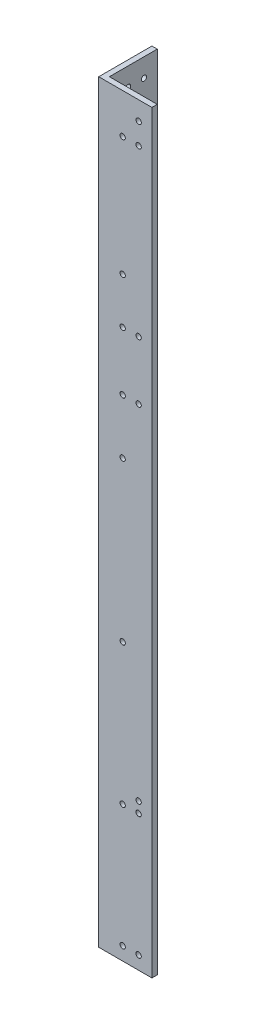
SolidWorks part; units mm, degrees
ref_plane "Front Plane" through (0, 0, 0) normal (0, 0, 1) x (1, 0, 0)
ref_plane "Top Plane" through (0, 0, 0) normal (0, 1, 0) x (1, 0, 0)
ref_plane "Right Plane" through (0, 0, 0) normal (1, 0, 0) x (0, 0, -1)
sketch "Sketch2" plane through (0, 0, 0) normal (0, 1, 0) x (1, 0, 0)
  line L0 (0, 31.75) -> (3.175, 31.75)
  line L1 (3.175, 31.75) -> (3.175, 3.175)
  line L2 (3.175, 3.175) -> (31.75, 3.175)
  line L3 (31.75, 3.175) -> (31.75, 0)
  line L4 (31.75, 0) -> (0, 0)
  line L5 (0, 0) -> (0, 31.75)
  point P9 (1.5875, 31.75)
  point P10 (31.75, 1.5875)
  dimension "D4" = 3.175
  dimension "D1" = 31.75
  dimension "D2" = 31.75
  dimension "D3" = 3.175
extrude "Boss-Extrude1" add sketch "Sketch2" along normal blind 450
sketch "LeftSideHoles-Sketch3" plane through (0, 0, 0) normal (0, 0, 1) x (1, 0, 0)
  line L0 (0, 0) -> (31.75, 0) construction
  line L1 (0, 450) -> (31.75, 450) construction
  line L3 (0, 450) -> (0, 0) construction
  circle A0 centre (14.2875, 81.1125) radius 1.5875
  circle A1 centre (23.8125, 81.1125) radius 1.5875
  circle A3 centre (23.8125, 87.4625) radius 1.5875
  circle A5 centre (14.2875, 426.1875) radius 1.5875
  circle A6 centre (23.8125, 438.8875) radius 1.5875
  circle A7 centre (23.8125, 426.1875) radius 1.5875
  circle A10 centre (14.2875, 327.6026) radius 1.5875
  circle A11 centre (23.8125, 327.6026) radius 1.5875
  circle A12 centre (14.2875, 292.6776) radius 1.5875
  circle A13 centre (23.8125, 292.6776) radius 1.5875
  circle A14 centre (14.2875, 7.9375) radius 1.5875
  circle A15 centre (23.8125, 7.9375) radius 1.5875
  circle A16 centre (14.2875, 165) radius 1.5875
  circle A17 centre (14.2875, 260) radius 1.5875
  circle A18 centre (14.2875, 355) radius 1.5875
  point P24 (15.875, 0)
  dimension "D4" = 3.175
  dimension "D1" = 81.1125
  dimension "D2" = 14.2875
  dimension "D10" = 7.9375
  dimension "D7" = 34.925
  dimension "D3" = 9.525
  dimension "D11" = 327.6026
  dimension "D12" = 165
  dimension "D13" = 95
  dimension "D14" = 95
  dimension "D5" = 6.35
  dimension "D6" = 12.7
  dimension "D8" = 11.1125
sketch "BackSideHoles-Sketch4" plane through (0, 0, 0) normal (-1, 0, 0) x (0, 0, 1)
  line L0 (-31.75, 450) -> (0, 450) construction
  line L2 (0, 450) -> (0, 0) construction
  line L3 (-31.75, 0) -> (0, 0) construction
  circle A0 centre (-23.8125, 81.1125) radius 1.5875
  circle A2 centre (-23.8125, 87.4625) radius 1.5875
  circle A3 centre (-14.2875, 87.4625) radius 1.5875
  circle A4 centre (-23.8125, 438.8875) radius 1.5875
  circle A5 centre (-14.2875, 438.8875) radius 1.5875
  circle A6 centre (-23.8125, 426.1875) radius 1.5875
  circle A10 centre (-23.8125, 327.6026) radius 1.5875
  circle A11 centre (-14.2875, 327.6026) radius 1.5875
  circle A12 centre (-23.8125, 321.2526) radius 1.5875
  circle A13 centre (-14.2875, 321.2526) radius 1.5875
  circle A14 centre (-14.2875, 165) radius 1.5875
  circle A15 centre (-14.2875, 260) radius 1.5875
  circle A16 centre (-14.2875, 355) radius 1.5875
  circle A17 centre (-23.8125, 7.9375) radius 1.5875
  circle A18 centre (-14.2875, 7.9375) radius 1.5875
  dimension "D4" = 3.175
  dimension "D2" = 14.2875
  dimension "D5" = 6.35
  dimension "D6" = 11.1125
  dimension "D8" = 6.35
  dimension "D7" = 12.7
  dimension "D1" = 327.6026
  dimension "D10" = 165
  dimension "D11" = 95
  dimension "D12" = 95
  dimension "D13" = 7.9375
  dimension "D3" = 81.1125
  dimension "D9" = 9.525
extrude "LeftSideHoles-Cut-Extrude1" cut sketch "LeftSideHoles-Sketch3" against normal blind 3.175
extrude "BackSideHoles-Cut-Extrude2" cut sketch "BackSideHoles-Sketch4" against normal blind 3.175
equation "\"RailThickness\"= .125in'Spec"
equation "\"VSWidth\"= 1.25in'Spec"
equation "\"VSHeight\"= 1.25in'Spec"
equation "\"VSLength\"= 450mm"
equation "\"HoleOffsetFromEdge\"= \"RailThickness\" * 2.5"
equation "\"HoleOffsetFromSide\"= \"RailThickness\" * 3.5"
equation "\"LegHeight\"= 70mm'Space needed for PSU/Stepper/Electronics"
equation "\"VSBottomSideRailHoleY1FromBottomOfLowerRail\"= \"V1 BottomOfLowerRail\" + \"HoleOffsetFromSide\"'Equals 70.1125"
equation "\"VSSideRailHoleX1FromSide\"= \"HoleOffsetFromSide\" + \"RailThickness\""
equation "\"FasteningHoleDiameter\"= .125in"
equation "\"VSBottomSideRailHoleY2FromY1\"= \"LowerRailHeight\" - \"HoleOffsetFromSide\" - \"HoleOffsetFromEdge\"'Equals 6.35"
equation "\"VSTopSideRailHoleY1FromEdge\"= \"HoleOffsetFromEdge\" + \"RailThickness\""
equation "\"D4@LeftSideHoles-Sketch3\"=\"FasteningHoleDiameter\""
equation "\"D1@LeftSideHoles-Sketch3\"=\"VSBottomSideRailHoleY1FromBottomOfLowerRail\""
equation "\"D2@LeftSideHoles-Sketch3\"=\"VSSideRailHoleX1FromSide\""
equation "\"D1@Boss-Extrude1\"=\"VSLength\""
equation "\"D4@BackSideHoles-Sketch4\" = \"FasteningHoleDiameter\""
equation "\"VSMidSideRailHoleY1FromV8TopOfMidSideRail\"= \"V8 ToTopOfMidSideRail\" - \"HoleOffsetFromEdge\"'Equals 308.2875"
equation "\"LowerRailHeight\"= 1.00in"
equation "\"D1@Sketch2\"=\"VSHeight\""
equation "\"D2@Sketch2\"=\"VSWidth\""
equation "\"MidBackRailHeight\"= 1.00in"
equation "\"VSMidBackRailHoleY1FromV7TopOfMidBackRail\"= \"V7 ToTopOfMidBackRail\" - \"HoleOffsetFromSide\"'Equals 308.2875"
equation "\"TopRailHeight\"= 1.25in"
equation "\"MidLeftOrRightSideRailHeight\"= 2.0in"
equation "\"D10@LeftSideHoles-Sketch3\"=\"HoleOffsetFromEdge\""
equation "\"VSMidBackRailHoleY2FromY1\"= \"MidBackRailHeight\" - \"HoleOffsetFromSide\" - \"HoleOffsetFromEdge\"'Equals 6.35"
equation "\"VSMidSideRailHoleY2FromY1\"= \"MidLeftOrRightSideRailHeight\" - \"HoleOffsetFromEdge\" * 2'Equals 34.925"
equation "\"D7@LeftSideHoles-Sketch3\"=\"VSMidSideRailHoleY2FromY1\""
equation "\"D8@BackSideHoles-Sketch4\"=\"VSMidBackRailHoleY2FromY1\""
equation "\"D6@BackSideHoles-Sketch4\"=\"VSTopSideRailHoleY1FromEdge\""
equation "\"VSTopSideRailHoleY2FromY1\"= \"TopRailHeight\" - \"VSTopSideRailHoleY1FromEdge\" - \"HoleOffsetFromEdge\"'Equals 12.7"
equation "\"D7@BackSideHoles-Sketch4\"=\"VSTopSideRailHoleY2FromY1\""
equation "\"VSBottomSideRailHoleX2FromX1\"= \"VSWidth\" - \"VSSideRailHoleX1FromSide\" - \"HoleOffsetFromEdge\""
equation "\"D3@LeftSideHoles-Sketch3\"=\"VSBottomSideRailHoleX2FromX1\""
equation "\"V1 BottomOfLowerRail\"= \"LegHeight\""
equation "\"StepperShaftLength\"= 24mm'Pulley will be attached to the end"
equation "\"ZAxisLeadScrewLength\"= 200mm"
equation "\"LM8UUHeight\"= 24mm'Spec"
equation "\"V2 ToBedAtTopOfZAxis\"= \"V1 BottomOfLowerRail\" - \"LowerEnclosureThickness\" + \"StepperShaftLength\" + \"ZAxisLeadScrewLength\" - \"LM8UUHeight\" / 2"
equation "\"HotEndToTopOfXAxisGB\"= 63.315144mm'Measured from the100.Should be 63.315144"
equation "\"TopOfGBToBottomOfLinearRail\"= \"LinearGBWidth\" / 2 + \"LinearRailWidth\" / 2"
equation "\"LinearGBWidth\"= 27mm'Spec"
equation "\"V5 ToBottomOfXAxisLinearRail\"= \"V4 ToTopOfBuildPlate/HotEndTip\" + \"HotEndToTopOfXAxisGB\" - \"TopOfGBToBottomOfLinearRail\""
equation "\"LinearRailWidth\"= 12mm'Spec"
equation "\"V6 ToBottomOfGantryPulley\"= \"V5 ToBottomOfXAxisLinearRail\" - \"DistanceFromGABTopToLowerPulley\""
equation "\"GABUpperHeight\"= 6mm"
equation "\"GABMidWallHeight\"= 28mm'Must equal 28 or changes alignment"
equation "\"20TGT2PulleyWidth\"= 8.7mm'The STL of the Pulley in the diagram is a bit larger"
equation "\"GABMidShortRiserHeight\"= \"GABMidWallHeight\" / 2 - \"20TGT2PulleyWidth\"'Equals 5.3"
equation "\"GABRiserBossOffset\"= 0.8mm'Aligns Pulleys"
equation "\"DistanceFromGABTopToLowerPulley\"= \"GABUpperHeight\" + \"GABMidWallHeight\" - \"GABMidShortRiserHeight\" + \"GABRiserBossOffset\" / 2"
equation "\"V7 ToTopOfMidBackRail\"= \"V6 ToBottomOfGantryPulley\" + \"StepperShaftLength\""
equation "\"D1@BackSideHoles-Sketch4\" = \"VSMidBackRailHoleY1FromV7TopOfMidBackRail\""
equation "\"D11@LeftSideHoles-Sketch3\"=\"VSMidSideRailHoleY1FromV8TopOfMidSideRail\""
equation "\"V4 ToTopOfBuildPlate/HotEndTip\"= \"V2 ToBedAtTopOfZAxis\" + \"BedToBuildPlateStandoffLength\" + \"BuildPlateHeight\""
equation "\"BedToBuildPlateStandoffLength\"= 15mm"
equation "\"BuildPlateHeight\"= 8mm'Spec"
equation "\"V8 ToTopOfMidSideRail\"= \"V7 ToTopOfMidBackRail\" - \"RailThickness\""
equation "\"VSEnclosureOffsets\"= ( \"VSLength\" - \"LegHeight\" ) / 4"
equation "\"D12@LeftSideHoles-Sketch3\"=\"LegHeight\" + \"VSEnclosureOffsets\""
equation "\"D13@LeftSideHoles-Sketch3\"=\"VSEnclosureOffsets\""
equation "\"D14@LeftSideHoles-Sketch3\"=\"VSEnclosureOffsets\""
equation "\"D10@BackSideHoles-Sketch4\"=\"LegHeight\" + \"VSEnclosureOffsets\""
equation "\"D11@BackSideHoles-Sketch4\"=\"VSEnclosureOffsets\""
equation "\"D12@BackSideHoles-Sketch4\"=\"VSEnclosureOffsets\""
equation "\"D13@BackSideHoles-Sketch4\"=\"HoleOffsetFromEdge\""
equation "\"D5@BackSideHoles-Sketch4\"=\"VSBottomSideRailHoleY2FromY1\""
equation "\"D3@BackSideHoles-Sketch4\"=\"VSBottomSideRailHoleY1FromBottomOfLowerRail\""
equation "\"D2@BackSideHoles-Sketch4\"=\"VSSideRailHoleX1FromSide\""
equation "\"D5@LeftSideHoles-Sketch3\"=\"VSBottomSideRailHoleY2FromY1\""
equation "\"D6@LeftSideHoles-Sketch3\"=\"VSTopSideRailHoleY2FromY1\""
equation "\"D8@LeftSideHoles-Sketch3\"=\"VSTopSideRailHoleY1FromEdge\""
equation "\"LowerEnclosureThickness\"= 5mm"
